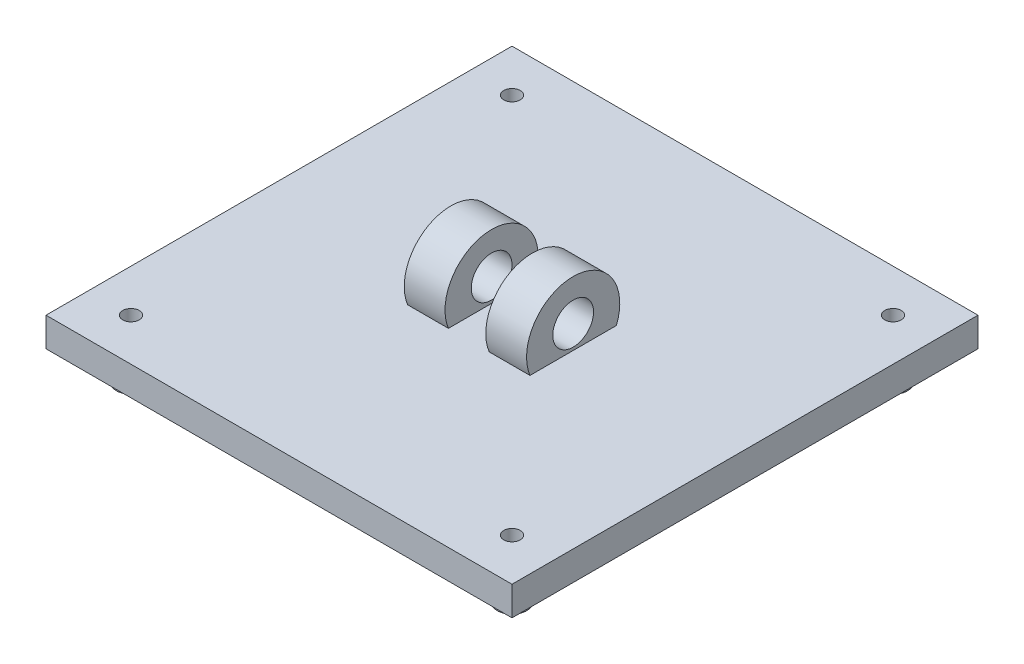
SolidWorks part; units mm, degrees
ref_plane "Front Plane" through (0, 0, 0) normal (0, 0, 1) x (1, 0, 0)
ref_plane "Top Plane" through (0, 0, 0) normal (0, 1, 0) x (1, 0, 0)
ref_plane "Right Plane" through (0, 0, 0) normal (1, 0, 0) x (0, 0, -1)
sketch "Sketch2" plane through (0, 0, 0) normal (0, 1, 0) x (1, 0, 0)
  line L1 (-40, -40) -> (40, -40)
  line L2 (-40, -40) -> (-40, 40)
  line L3 (-40, 40) -> (40, 40)
  line L4 (40, -40) -> (40, 40)
  line L5 (-40, -40) -> (40, 40) construction
  line L6 (-40, 40) -> (40, -40) construction
  point P0 (0, 0)
  dimension "D1" = 80
  dimension "D2" = 80
extrude "Boss-Extrude1" add sketch "Sketch2" along normal blind 5
sketch "Sketch3" plane through (0, 0, 0) normal (1, 0, 0) x (0, 0, -1)
  line L0 (-40, 0) -> (40, 0) construction
  line L1 (0, 0) -> (0.4848, 0)
  circle A0 centre (0, 8) radius 8
  dimension "D1" = 16
  dimension "D2" = 8
extrude "Boss-Extrude2" add sketch "Sketch3" along normal mid plane 21 contours A0 region at (0, 8, 0)
sketch "Sketch4" plane through (0, 0, 0) normal (1, 0, 0) x (0, 0, -1)
  line L0 (-7.4162, 5) -> (7.4162, 5)
  circle A1 centre (0, 8) radius 8
  arc A2 (7.4162, 5) -> (-7.4162, 5) centre (0, 8) ccw construction
extrude "Cut-Extrude3" cut sketch "Sketch4" against normal mid plane 7 contours L0 A1 region at (0, 9.8451, 0)
sketch "Sketch8" plane through (10.5, 0, 0) normal (1, 0, 0) x (0, 0, -1)
  line L1 (7.4162, 5) -> (-7.4162, 5) construction
  circle A0 centre (0, 9) radius 3.5
  dimension "D1" = 7
  dimension "D2" = 4
extrude "Cut-Extrude5" cut sketch "Sketch8" against normal through all
sketch "Sketch9" plane through (0, 0, 0) normal (0, -1, 0) x (1, 0, 0)
  line L0 (0, 0) -> (0, -40)
  line L1 (40, -40) -> (-40, -40) construction
  circle A0 centre (-32.705, 32.705) radius 2.5
  circle A1 centre (32.705, 32.705) radius 2.5
  circle A2 centre (-32.705, -32.705) radius 2.5
  circle A3 centre (32.705, -32.705) radius 2.5
  point P13 (0, 0)
  point P14 (0, 0)
  dimension "D2" = 32.705
  dimension "D3" = 5
  dimension "D5" = 32.705
  dimension "D1" = 32.705
  dimension "D4" = 32.705
extrude "Boss-Extrude3" add sketch "Sketch9" along normal blind 5 contours A0 | A1 | A3 | A2
sketch "Sketch10" plane through (0, -5, 0) normal (0, -1, 0) x (1, 0, 0)
  circle A0 centre (-32.705, -32.705) radius 1.41
  circle A1 centre (-32.705, 32.705) radius 1.41
  circle A2 centre (32.705, 32.705) radius 1.41
  circle A3 centre (32.705, -32.705) radius 1.41
  dimension "D1" = 2.82
extrude "Cut-Extrude6" cut sketch "Sketch10" against normal through all
equation "\"D2@Sketch3\"=\"D1@Sketch3\"/2"
